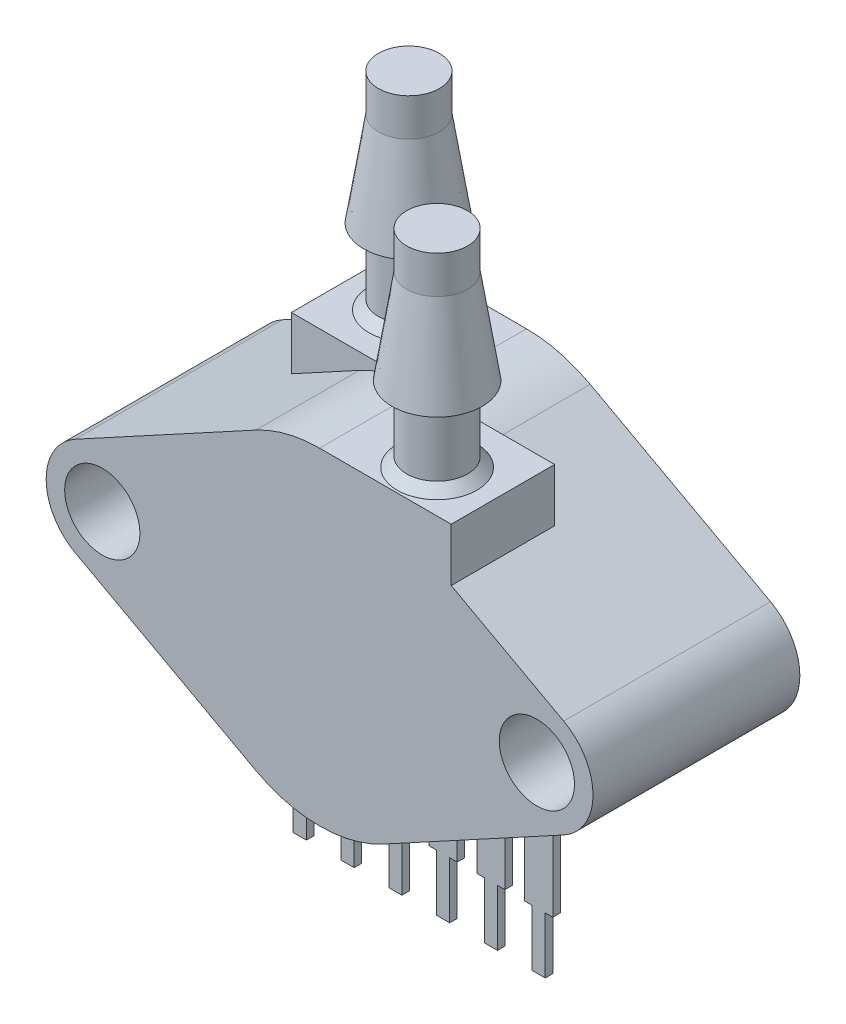
SolidWorks part; units mm, degrees
ref_plane "Plan de face" through (0, 0, 0) normal (0, 0, 1) x (1, 0, 0)
ref_plane "Plan de dessus" through (0, 0, 0) normal (0, 1, 0) x (1, 0, 0)
ref_plane "Plan de droite" through (0, 0, 0) normal (1, 0, 0) x (0, 0, -1)
sketch "Esquisse1" plane through (0, 0, 0) normal (0, 0, 1) x (1, 0, 0)
  line L0 (0, 0) -> (0, 1.6004) construction
  line L1 (0, 0) -> (11.555, 0) construction
  line L2 (3.3919, 7.8373) -> (12.9811, 2.6223)
  line L3 (3.3919, -7.8373) -> (12.9811, -2.6223)
  line L4 (-3.3919, 7.8373) -> (-12.9811, 2.6223)
  line L5 (-3.3919, -7.8373) -> (-12.9811, -2.6223)
  arc A0 (3.3919, 7.8373) -> (-3.3919, 7.8373) centre (0, 1.6004) ccw
  arc A1 (12.9811, 2.6223) -> (12.9811, -2.6223) centre (11.555, 0) cw
  arc A2 (3.3919, -7.8373) -> (-3.3919, -7.8373) centre (0, -1.6004) cw
  arc A3 (-12.9811, 2.6223) -> (-12.9811, -2.6223) centre (-11.555, 0) ccw
  circle A4 centre (11.555, 0) radius 2
  circle A5 centre (-11.555, 0) radius 2
  point P15 (0, 0)
  point P17 (-2.7305, 8.0205)
  point P18 (0, 8.7)
  point P19 (0, -8.7)
  point P20 (-14.54, 0)
  point P21 (14.54, 0)
  dimension "D4" = 4
  dimension "D1" = 23.11
  dimension "D2" = 17.4
  dimension "D3" = 29.08
extrude "Boss.-Extru.1" add sketch "Esquisse1" along normal mid plane 11
ref_plane "Plan1" through (0, 8.7, 0) normal (0, 1, 0) x (1, 0, 0)
sketch "Esquisse3" plane through (0, 0, 5.5) normal (0, 0, 1) x (1, 0, 0)
  line L0 (0, 8.7) -> (7, 8.7)
  line L1 (5.3843, 8.7) -> (-5.3843, 8.7) construction
  line L2 (7, 8.7) -> (7, 5.8751)
  line L5 (12.9811, 2.6223) -> (3.3919, 7.8373) construction
  line L6 (7, 5.8751) -> (3.3919, 7.8373)
  arc A0 (3.3919, 7.8373) -> (-3.3919, 7.8373) centre (0, 1.6004) ccw construction
  arc A2 (3.3919, 7.8373) -> (0, 8.7) centre (0, 1.6004) ccw
  point P4 (7, 5.8751)
  dimension "D1" = 7
extrude "Boss.-Extru.3" add sketch "Esquisse3" against normal blind 5.5
ref_axis "Axe1" through (0, -10.12, 0) along (0, 1, 0)
ref_plane "Plan2" through (0, 0, 3.25) normal (0, 0, 1) x (1, 0, 0)
ref_plane "Plan3" through (4, 0, 0) normal (1, 0, 0) x (0, 0, -1)
ref_axis "Axe2" through (4, 8.3763, 3.25) along (0, 1, 0)
sketch "Esquisse4" plane through (0, 0, 3.25) normal (0, 0, 1) x (1, 0, 0)
  line L15 (4, 8.7) -> (4, 19.7)
  line L16 (5.3843, 8.7) -> (-5.3843, 8.7) construction
  line L17 (4, 8.3763) -> (4, 14.8958) construction
  line L18 (4, -2.2767) -> (4, 2.2767) construction
  line L19 (4, 19.7) -> (2.3783, 19.7)
  line L20 (2.3783, 19.7) -> (2.3783, 17.7)
  line L21 (2.3783, 17.7) -> (1.6, 12.7)
  line L22 (1.6, 12.7) -> (2.3783, 12.7)
  line L23 (2.3783, 12.7) -> (2.3783, 8.7)
  line L24 (2.3783, 8.7) -> (4, 8.7)
  dimension "D1" = 2.4
  dimension "D2" = 4
  dimension "D3" = 11
  dimension "D4" = 2
revolve "Révolution1" add sketch "Esquisse4" angle 360 about L15
pattern_circular "Répétition circulaire1" count 2 over 360 about axis through (0, -10.12, 0) along (0, 1, 0) of "Boss.-Extru.3", "Révolution1"
chamfer "Chanfrein1" distance 0.5 angle 45 2 edges at (-4, 8.7, -1.6283) (4, 8.7, 1.6283)
sketch "Esquisse5" plane through (0, 0, 0) normal (0, -1, 0) x (-1, 0, 0)
  line L0 (0, 0) -> (0.52, 0) construction
  line L2 (0.52, 0.2) -> (2.02, 0.2)
  line L3 (0.52, 0.2) -> (0.52, -0.2)
  line L4 (0.52, -0.2) -> (2.02, -0.2)
  line L5 (2.02, 0.2) -> (2.02, -0.2)
  line L6 (2.02, 0) -> (3.06, 0) construction
  line L7 (4.56, 0) -> (5.6, 0) construction
  line L8 (3.06, 0.2) -> (4.56, 0.2)
  line L9 (3.06, 0.2) -> (3.06, -0.2)
  line L10 (3.06, -0.2) -> (4.56, -0.2)
  line L11 (4.56, 0.2) -> (4.56, -0.2)
  line L12 (0, 0) -> (0, 0.9956) construction
  line L13 (5.6, 0.2) -> (7.1, 0.2)
  line L14 (5.6, 0.2) -> (5.6, -0.2)
  line L15 (5.6, -0.2) -> (7.1, -0.2)
  line L16 (7.1, 0.2) -> (7.1, -0.2)
  line L17 (-5.6, -0.2) -> (-7.1, -0.2)
  line L18 (-7.1, 0.2) -> (-7.1, -0.2)
  line L19 (-5.6, 0.2) -> (-7.1, 0.2)
  line L20 (-5.6, 0.2) -> (-5.6, -0.2)
  line L21 (-3.06, -0.2) -> (-4.56, -0.2)
  line L22 (-4.56, 0.2) -> (-4.56, -0.2)
  line L23 (-3.06, 0.2) -> (-4.56, 0.2)
  line L24 (-3.06, 0.2) -> (-3.06, -0.2)
  line L25 (-0.52, -0.2) -> (-2.02, -0.2)
  line L26 (-2.02, 0.2) -> (-2.02, -0.2)
  line L27 (-0.52, 0.2) -> (-2.02, 0.2)
  line L28 (-0.52, 0.2) -> (-0.52, -0.2)
  point P7 (-1.27, 0.2)
  point P8 (1.27, 0.2)
  point P9 (0.52, 0)
  point P17 (3.06, 0)
  point P23 (5.6, 0)
  point P37 (3.81, -0.2)
  point P38 (6.35, -0.2)
  dimension "D1" = 0.4
  dimension "D2" = 1.5
  dimension "D3" = 2.54
  dimension "D4" = 2.54
extrude "Boss.-Extru.4" add sketch "Esquisse5" along normal blind 12 separate body
sketch "Esquisse6" plane through (0, -12, 0) normal (0, -1, 0) x (1, 0, 0)
  line L1 (6, 0.2) -> (6.7, 0.2)
  line L2 (6, 0.2) -> (6, -0.2)
  line L3 (6, -0.2) -> (6.7, -0.2)
  line L4 (6.7, 0.2) -> (6.7, -0.2)
  line L6 (7.1, 0.2) -> (5.6, 0.2) construction
  line L7 (5.6, -0.2) -> (7.1, -0.2) construction
  line L8 (3.46, 0.2) -> (3.46, -0.2)
  line L9 (3.46, 0.2) -> (4.16, 0.2)
  line L10 (4.16, 0.2) -> (4.16, -0.2)
  line L11 (3.46, -0.2) -> (4.16, -0.2)
  line L12 (0.92, 0.2) -> (0.92, -0.2)
  line L13 (0.92, 0.2) -> (1.62, 0.2)
  line L14 (1.62, 0.2) -> (1.62, -0.2)
  line L15 (0.92, -0.2) -> (1.62, -0.2)
  line L16 (-1.62, 0.2) -> (-1.62, -0.2)
  line L17 (-1.62, 0.2) -> (-0.92, 0.2)
  line L18 (-0.92, 0.2) -> (-0.92, -0.2)
  line L19 (-1.62, -0.2) -> (-0.92, -0.2)
  line L20 (-4.16, 0.2) -> (-4.16, -0.2)
  line L21 (-4.16, 0.2) -> (-3.46, 0.2)
  line L22 (-3.46, 0.2) -> (-3.46, -0.2)
  line L23 (-4.16, -0.2) -> (-3.46, -0.2)
  line L24 (-6.7, 0.2) -> (-6.7, -0.2)
  line L25 (-6.7, 0.2) -> (-6, 0.2)
  line L26 (-6, 0.2) -> (-6, -0.2)
  line L27 (-6.7, -0.2) -> (-6, -0.2)
  point P4 (6.35, 0.2)
  point P7 (6.35, 0.2)
  point P11 (4.1667, 0.2)
  point P32 (4.1777, -0.2)
  point P33 (3.81, -0.2)
  point P34 (6.35, -0.2)
  dimension "D1" = 0.7
  dimension "D3" = 2.54
  dimension "D2" = 6
extrude "Boss.-Extru.5" add sketch "Esquisse6" along normal blind 3
equation "\"D4@Esquisse5\"=\"D3@Esquisse5\""
